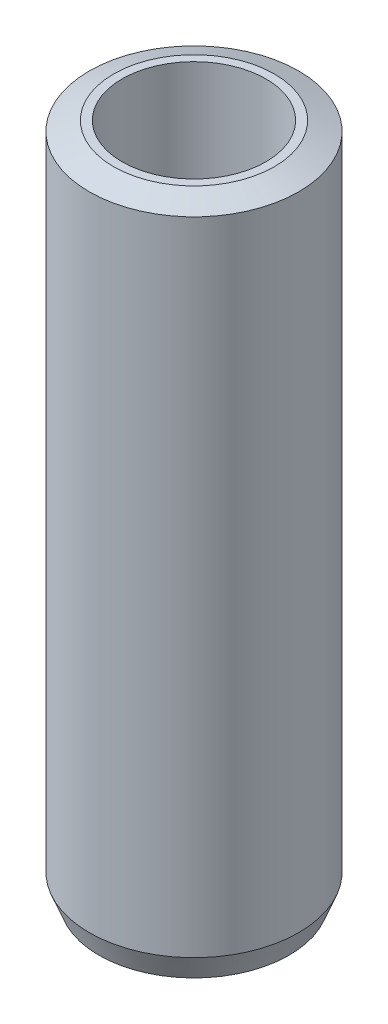
SolidWorks part; units mm, degrees
ref_plane "Front Plane" through (0, 0, 0) normal (0, 0, 1) x (1, 0, 0)
ref_plane "Top Plane" through (0, 0, 0) normal (0, 1, 0) x (1, 0, 0)
ref_plane "Right Plane" through (0, 0, 0) normal (1, 0, 0) x (0, 0, -1)
sketch "Sketch1" plane through (0, 0, 0) normal (0, 1, 0) x (1, 0, 0)
  circle A0 centre (0, 0) radius 45
  dimension "SHAFT_OD" = 90
extrude "Boss-Extrude1" add sketch "Sketch1" along normal blind 290.3022
sketch "Sketch2" plane through (0, 0, 0) normal (0, 1, 0) x (1, 0, 0)
  circle A0 centre (0, 0) radius 30.9024
  dimension "BORE_D" = 61.8049
extrude "Cut-Extrude1" cut sketch "Sketch2" along normal through all
chamfer "Chamfer1" distance 4.1071 angle 68.552 2 edges at (0, 290.3022, 45) (0, 0, 45) first distance on face at (0, 290.3022, 45) first distance on face at (0, 0, 30.9024)
